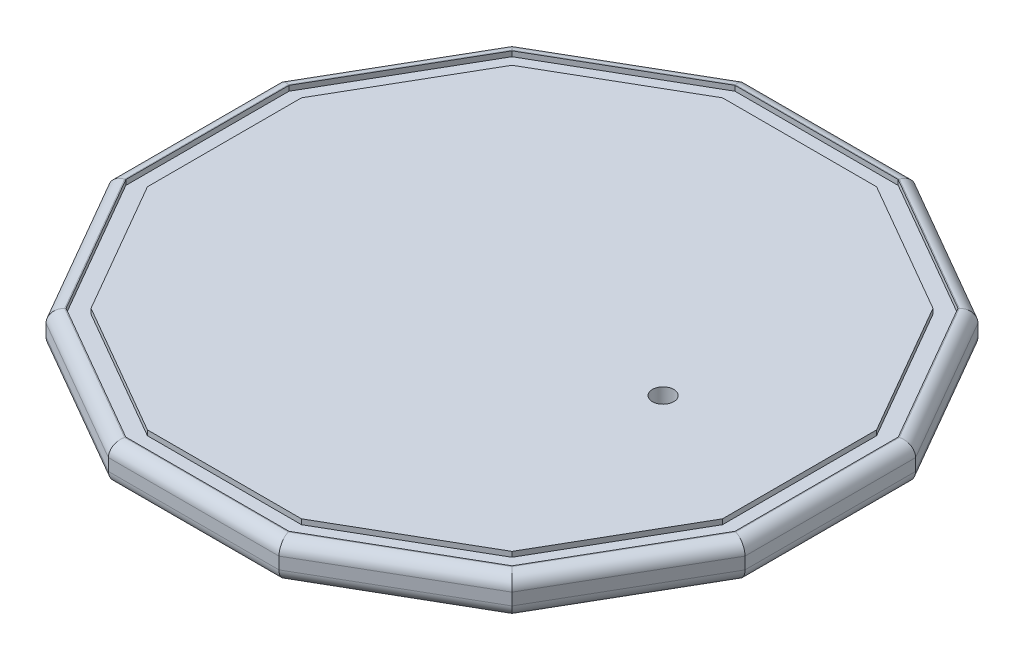
SolidWorks part; units mm, degrees
ref_plane "정면" through (0, 0, 0) normal (0, 0, 1) x (1, 0, 0)
ref_plane "윗면" through (0, 0, 0) normal (0, 1, 0) x (1, 0, 0)
ref_plane "우측면" through (0, 0, 0) normal (1, 0, 0) x (0, 0, -1)
sketch "스케치1" plane through (0, 0, 0) normal (0, 1, 0) x (1, 0, 0)
  line L1 (27.2932, -27.2932) -> (37.2832, -9.99)
  line L2 (37.2832, -9.99) -> (37.2832, 9.99)
  line L3 (37.2832, 9.99) -> (27.2932, 27.2932)
  line L4 (27.2932, 27.2932) -> (9.99, 37.2832)
  line L5 (9.99, 37.2832) -> (-9.99, 37.2832)
  line L6 (-9.99, 37.2832) -> (-27.2932, 27.2932)
  line L7 (-27.2932, 27.2932) -> (-37.2832, 9.99)
  line L8 (-37.2832, 9.99) -> (-37.2832, -9.99)
  line L9 (-37.2832, -9.99) -> (-27.2932, -27.2932)
  line L10 (-27.2932, -27.2932) -> (-9.99, -37.2832)
  line L11 (-9.99, -37.2832) -> (9.99, -37.2832)
  line L12 (9.99, -37.2832) -> (27.2932, -27.2932)
  circle A0 centre (0, 0) radius 37.2832 construction
  dimension "D1" = 19.98
extrude "보스-돌출1" add sketch "스케치1" along normal blind 4.4
sketch "스케치2" plane through (0, 4.4, 0) normal (0, 1, 0) x (1, 0, 0)
  line L0 (-26.1209, 26.1209) -> (-35.6818, 9.5609)
  line L1 (24.6568, -24.6568) -> (33.6818, -9.025)
  line L2 (33.6818, -9.025) -> (33.6818, 9.025)
  line L3 (33.6818, 9.025) -> (24.6568, 24.6568)
  line L4 (24.6568, 24.6568) -> (9.025, 33.6818)
  line L5 (9.025, 33.6818) -> (-9.025, 33.6818)
  line L6 (-9.025, 33.6818) -> (-24.6568, 24.6568)
  line L7 (-24.6568, 24.6568) -> (-33.6818, 9.025)
  line L8 (-33.6818, 9.025) -> (-33.6818, -9.025)
  line L9 (-33.6818, -9.025) -> (-24.6568, -24.6568)
  line L10 (-24.6568, -24.6568) -> (-9.025, -33.6818)
  line L11 (-9.025, -33.6818) -> (9.025, -33.6818)
  line L12 (9.025, -33.6818) -> (24.6568, -24.6568)
  line L13 (-35.6818, 9.5609) -> (-35.6818, -9.5609)
  line L14 (-35.6818, -9.5609) -> (-26.1209, -26.1209)
  line L15 (-26.1209, -26.1209) -> (-9.5609, -35.6818)
  line L16 (-9.5609, -35.6818) -> (9.5609, -35.6818)
  line L17 (9.5609, -35.6818) -> (26.1209, -26.1209)
  line L18 (26.1209, -26.1209) -> (35.6818, -9.5609)
  line L19 (35.6818, -9.5609) -> (35.6818, 9.5609)
  line L20 (35.6818, 9.5609) -> (26.1209, 26.1209)
  line L21 (26.1209, 26.1209) -> (9.5609, 35.6818)
  line L22 (9.5609, 35.6818) -> (-9.5609, 35.6818)
  line L23 (-9.5609, 35.6818) -> (-26.1209, 26.1209)
  circle A0 centre (0, 0) radius 33.6818 construction
  dimension "D1" = 18.05
  dimension "D2" = 2
extrude "컷-돌출1" cut sketch "스케치2" against normal blind 0.6
fillet "필렛1" radius 1.5 24 edges at (-32.2882, 0, 18.6416) (-37.2832, 0, 0) (-32.2882, 0, -18.6416) (-18.6416, 0, -32.2882) (0, 0, -37.2832) (18.6416, 0, -32.2882) (32.2882, 0, -18.6416) (-32.2882, 4.4, 18.6416) (-37.2832, 4.4, 0) (-32.2882, 4.4, -18.6416) (-18.6416, 4.4, -32.2882) (0, 4.4, -37.2832) (18.6416, 4.4, -32.2882) (32.2882, 4.4, -18.6416) (37.2832, 4.4, 0) (37.2832, 0, 0) (32.2882, 4.4, 18.6416) (32.2882, 0, 18.6416) (18.6416, 0, 32.2882) (18.6416, 4.4, 32.2882) (0, 0, 37.2832) (0, 4.4, 37.2832) (-18.6416, 0, 32.2882) (-18.6416, 4.4, 32.2882)
sketch "스케치3" plane through (0, 0, 0) normal (0, -1, 0) x (1, 0, 0)
  line L0 (0, 0) -> (0, 15) construction
  line L1 (0, 0) -> (0, -15) construction
  line L3 (-2.5, -10.5) -> (2.5, -10.5)
  line L4 (-2.5, -10.5) -> (-2.5, -19.5)
  line L5 (-2.5, -19.5) -> (2.5, -19.5)
  line L6 (2.5, -10.5) -> (2.5, -19.5)
  line L7 (-2.5, -10.5) -> (2.5, -19.5) construction
  line L8 (-2.5, -19.5) -> (2.5, -10.5) construction
  line L9 (2.5, 19.5) -> (-2.5, 19.5)
  line L10 (2.5, 19.5) -> (2.5, 10.5)
  line L11 (2.5, 10.5) -> (-2.5, 10.5)
  line L12 (-2.5, 19.5) -> (-2.5, 10.5)
  line L13 (2.5, 19.5) -> (-2.5, 10.5) construction
  line L14 (2.5, 10.5) -> (-2.5, 19.5) construction
  dimension "D1" = 15
  dimension "D2" = 9
  dimension "D3" = 5
extrude "보스-돌출2" add sketch "스케치3" along normal blind 14.5
fillet "필렛2" radius 4.5 4 edges at (0, -14.5, -19.5) (0, -14.5, -10.5) (0, -14.5, 19.5) (0, -14.5, 10.5)
sketch "스케치4" plane through (-2.5, 0, 0) normal (-1, 0, 0) x (0, 0, 1)
  circle A0 centre (-15, -10) radius 1.55
  circle A1 centre (15, -10) radius 1.55
  dimension "D1" = 3.1
extrude "컷-돌출2" cut sketch "스케치4" against normal through all both and the other way through all
sketch "스케치5" plane through (0, 0, 0) normal (0, -1, 0) x (1, 0, 0)
  line L0 (0, 0) -> (17.7, 0) construction
  circle A0 centre (17.7, 0) radius 1.25
  dimension "D2" = 2.5
  dimension "D1" = 17.7
extrude "컷-돌출3" cut sketch "스케치5" against normal through all both
